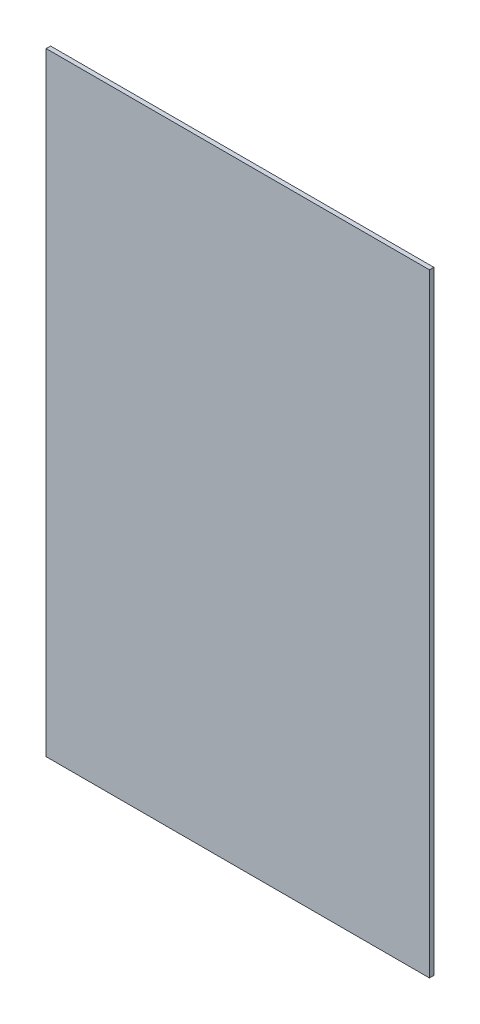
SolidWorks part; units mm, degrees
material "AISI 1020"
ref_plane "Front Plane" through (0, 0, 0) normal (0, 0, 1) x (1, 0, 0)
ref_plane "Top Plane" through (0, 0, 0) normal (0, 1, 0) x (1, 0, 0)
ref_plane "Right Plane" through (0, 0, 0) normal (1, 0, 0) x (0, 0, -1)
sketch "Sketch1" plane through (0, 0, 0) normal (0, 0, 1) x (1, 0, 0)
  line L1 (-39.6875, -63.5) -> (39.6875, -63.5)
  line L2 (-39.6875, -63.5) -> (-39.6875, 63.5)
  line L3 (-39.6875, 63.5) -> (39.6875, 63.5)
  line L4 (39.6875, -63.5) -> (39.6875, 63.5)
  line L5 (-39.6875, -63.5) -> (39.6875, 63.5) construction
  line L6 (-39.6875, 63.5) -> (39.6875, -63.5) construction
  point P0 (0, 0)
  dimension "D1" = 79.375
  dimension "D2" = 127
base flange "Base-Flange1" sketch "Sketch1" thickness 0.9119 reverse thickness direction no parameters "D1"=6.35
sketch "Bend-Lines1" [suppressed] plane through (0, 0, 0) normal (0, 1, 0) x (1, 0, 0)
sketch "Bounding-Box1" [suppressed] plane through (0, 0, 0) normal (0, 1, 0) x (1, 0, 0)
sheet metal parameters "Sheet-Metal1" thickness 0.9119 parameters "D1"=6.35
flat pattern "Flat-Pattern1" [suppressed]
sketch "Bend-Lines2" plane through (0, 0, 0) normal (0, 1, 0) x (1, 0, 0)
sketch3d "Bounding-Box2" [suppressed]
  line L0 (-39.6875, 63.5, 0) -> (-39.6875, -63.5, 0) construction
  line L1 (39.6875, 63.5, 0) -> (39.6875, -63.5, 0) construction
  line L2 (-39.6875, 63.5, 0) -> (39.6875, 63.5, 0) construction
  line L3 (-39.6875, -63.5, 0) -> (39.6875, -63.5, 0) construction
